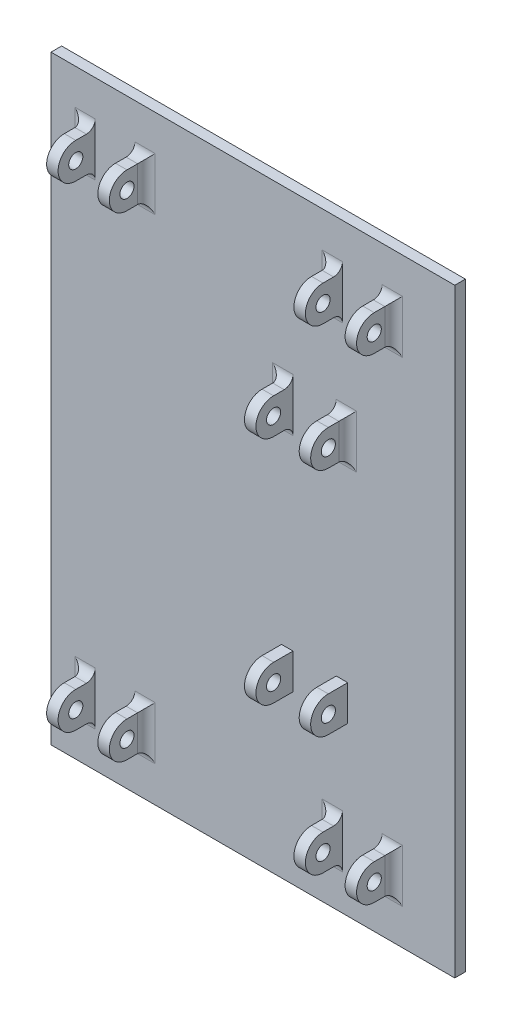
SolidWorks part; units mm, degrees
other "Markup3"
sketch "Sketch7" plane through (228.6, -342.9, 31.75) normal (0.076, -0.0024, 0.9971) x (0.9961, 0.0458, -0.0758)
other "Markup4"
sketch "Sketch8" plane through (228.6, -342.9, 31.75) normal (0.076, -0.0024, 0.9971) x (0.9961, 0.0458, -0.0758)
material "7075-T6 (SN)"
ref_plane "Front Plane" through (0, 0, 0) normal (0, 0, 1) x (1, 0, 0)
ref_plane "Top Plane" through (0, 0, 0) normal (0, 1, 0) x (1, 0, 0)
ref_plane "Right Plane" through (0, 0, 0) normal (1, 0, 0) x (0, 0, -1)
sketch "Sketch1" plane through (0, 0, 0) normal (0, 0, 1) x (1, 0, 0)
  line L1 (0, 0) -> (228.6, 0)
  line L2 (0, 0) -> (0, -339.725)
  line L3 (0, -339.725) -> (228.6, -339.725)
  line L4 (228.6, 0) -> (228.6, -339.725)
  dimension "D1" = 339.725
  dimension "D2" = 228.6
extrude "Boss-Extrude1" add sketch "Sketch1" along normal blind 6
sketch "Sketch2" plane through (0, 0, 6) normal (0, 0, 1) x (1, 0, 0)
  line L0 (0, 0) -> (0, -339.725) construction
  line L1 (25, -25.2425) -> (47.5, -25.2425) construction
  line L2 (25, -25.2425) -> (25, -45.2425)
  line L3 (25, -45.2425) -> (47.5, -45.2425) construction
  line L4 (47.5, -25.2425) -> (47.5, -45.2425)
  line L5 (165, -25.2425) -> (187.5, -25.2425) construction
  line L6 (165, -25.2425) -> (165, -45.2425)
  line L7 (165, -45.2425) -> (187.5, -45.2425) construction
  line L8 (187.5, -25.2425) -> (187.5, -45.2425)
  line L18 (137.0009, -114.5325) -> (137.0009, -225.1925) construction
  line L19 (0, -169.8625) -> (106.25, -169.8625) construction
  line L20 (54, -35.2425) -> (158.5, -35.2425) construction
  line L26 (165, -25.2425) -> (158.5, -25.2425)
  line L27 (165, -25.2425) -> (165, -45.2425)
  line L28 (165, -45.2425) -> (158.5, -45.2425)
  line L29 (158.5, -25.2425) -> (158.5, -45.2425)
  line L30 (187.5, -25.2425) -> (194, -25.2425)
  line L31 (187.5, -25.2425) -> (187.5, -45.2425)
  line L32 (187.5, -45.2425) -> (194, -45.2425)
  line L33 (194, -25.2425) -> (194, -45.2425)
  line L34 (47.5, -25.2425) -> (54, -25.2425)
  line L35 (47.5, -25.2425) -> (47.5, -45.2425)
  line L36 (47.5, -45.2425) -> (54, -45.2425)
  line L37 (54, -25.2425) -> (54, -45.2425)
  line L38 (25, -25.2425) -> (18.5, -25.2425)
  line L39 (25, -25.2425) -> (25, -45.2425)
  line L40 (25, -45.2425) -> (18.5, -45.2425)
  line L41 (18.5, -25.2425) -> (18.5, -45.2425)
  line L65 (228.6, -339.725) -> (228.6, 0) construction
  line L66 (137.0009, -225.1925) -> (161.5009, -225.1925) construction
  line L67 (158.5, -304.4825) -> (194, -304.4825) construction
  line L68 (149.2509, -104.5325) -> (149.2509, -229.5652) construction
  line L76 (18.5, -35.2425) -> (54, -35.2425) construction
  line L77 (18.5, -304.4825) -> (54, -304.4825) construction
  line L78 (36.25, -35.2425) -> (36.25, -304.4825) construction
  line L79 (137.0009, -94.5325) -> (161.5009, -94.5325) construction
  line L80 (54, -304.4825) -> (158.5, -304.4825) construction
  line L81 (106.25, -35.2425) -> (106.25, -304.4825) construction
  line L82 (106.25, -169.8625) -> (228.6, -169.8625) construction
  line L83 (130.5009, -94.5325) -> (130.5009, -114.5325)
  line L84 (137.0009, -114.5325) -> (130.5009, -114.5325)
  line L86 (137.0009, -94.5325) -> (130.5009, -94.5325)
  line L88 (137.0009, -94.5325) -> (137.0009, -114.5325)
  line L89 (161.5009, -114.5325) -> (168.0009, -114.5325)
  line L90 (161.5009, -114.5325) -> (161.5009, -94.5325)
  line L91 (168.0009, -94.5325) -> (168.0009, -114.5325)
  line L92 (161.5009, -94.5325) -> (168.0009, -94.5325)
  line L93 (130.5009, -235.1925) -> (168.0009, -235.1925) construction
  line L96 (137.0009, -245.1925) -> (161.5009, -245.1925) construction
  line L97 (161.5009, -245.1925) -> (168.0009, -245.1925)
  line L98 (168.0009, -245.1925) -> (168.0009, -225.1925)
  line L103 (130.5009, -104.5325) -> (168.0009, -104.5325) construction
  line L104 (137.0009, -114.5325) -> (161.5009, -114.5325) construction
  line L106 (158.5, -35.2425) -> (194, -35.2425) construction
  line L108 (176.25, -35.2425) -> (176.25, -304.4825) construction
  line L109 (165, -294.4825) -> (187.5, -294.4825) construction
  line L112 (165, -314.4825) -> (187.5, -314.4825) construction
  line L113 (25, -294.4825) -> (47.5, -294.4825) construction
  line L114 (25, -314.4825) -> (47.5, -314.4825) construction
  line L117 (161.5009, -114.5325) -> (161.5009, -225.1925) construction
  line L118 (18.5, -314.4825) -> (18.5, -294.4825)
  line L119 (25, -294.4825) -> (18.5, -294.4825)
  line L120 (25, -314.4825) -> (25, -294.4825)
  line L121 (25, -314.4825) -> (18.5, -314.4825)
  line L122 (54, -314.4825) -> (54, -294.4825)
  line L123 (47.5, -294.4825) -> (54, -294.4825)
  line L124 (47.5, -314.4825) -> (47.5, -294.4825)
  line L125 (47.5, -314.4825) -> (54, -314.4825)
  line L126 (194, -314.4825) -> (194, -294.4825)
  line L127 (187.5, -294.4825) -> (194, -294.4825)
  line L128 (187.5, -314.4825) -> (187.5, -294.4825)
  line L129 (187.5, -314.4825) -> (194, -314.4825)
  line L130 (158.5, -314.4825) -> (158.5, -294.4825)
  line L131 (165, -294.4825) -> (158.5, -294.4825)
  line L132 (165, -314.4825) -> (165, -294.4825)
  line L133 (165, -314.4825) -> (158.5, -314.4825)
  line L134 (187.5, -314.4825) -> (187.5, -294.4825)
  line L135 (165, -314.4825) -> (165, -294.4825)
  line L136 (47.5, -314.4825) -> (47.5, -294.4825)
  line L137 (25, -314.4825) -> (25, -294.4825)
  line L138 (161.5009, -225.1925) -> (161.5009, -245.1925)
  line L139 (161.5009, -225.1925) -> (168.0009, -225.1925)
  line L140 (137.0009, -245.1925) -> (137.0009, -225.1925)
  line L141 (137.0009, -245.1925) -> (130.5009, -245.1925)
  line L142 (137.0009, -225.1925) -> (130.5009, -225.1925)
  line L143 (130.5009, -245.1925) -> (130.5009, -225.1925)
  point P63 (194, -35.2425)
  point P70 (0, 0)
  point P101 (228.6, -169.8625)
  point P103 (158.5, -35.2425)
  dimension "D5" = 43.0009
  dimension "D1" = 20
  dimension "D2" = 22.5
  dimension "D3" = 6.5
  dimension "D4" = 199.95
  dimension "D6" = 134.62
  dimension "D7" = 134.62
  dimension "D8" = 24.5
  dimension "D9" = 70
  dimension "D10" = 25
extrude "Boss-Extrude2" add sketch "Sketch2" along normal blind 24 contours L133 L132 L131 L130 | L128 L129 L126 L127 | L139 L138 L97 L98 | L143 L141 L140 L142 | L124 L125 L122 L123 | L121 L120 L119 L118 | L92 L90 L89 L91 | L88 L86 L83 L84 | L33 L30 L8 L32 | L37 L34 L4 L36 | L38 L41 L40 L2 | L26 L29 L28 L27 region at (21.75, -35.2425, 6) region at (50.75, -35.2425, 6) region at (190.75, -35.2425, 6) region at (133.7509, -104.5325, 6) region at (164.7509, -104.5325, 6) region at (164.7509, -235.1925, 6) region at (21.75, -304.4825, 6) region at (50.75, -304.4825, 6) region at (190.75, -304.4825, 6) region at (161.75, -304.4825, 6) region at (133.7509, -235.1925, 6)
sketch "Sketch3" plane through (18.5, 0, 0) normal (-1, 0, 0) x (0, 0, 1)
  line L0 (17, -104.5325) -> (6, -104.5325) construction
  line L1 (17, -304.4825) -> (6, -304.4825) construction
  line L2 (21, -235.1925) -> (37.7332, -235.1925) construction
  line L3 (21, -235.1925) -> (6, -235.1925) construction
  line L4 (17, -35.2425) -> (6, -35.2425) construction
  line L5 (6, -25.2425) -> (6, -45.2425) construction
  line L6 (6, -245.1925) -> (6, -225.1925) construction
  line L7 (6, 0) -> (6, -339.725) construction
  line L9 (17, -25.2425) -> (17, -12.9829)
  line L10 (17, -12.9829) -> (50.9495, -12.9829)
  line L11 (6, -245.1925) -> (6, -225.1925) construction
  line L12 (50.9495, -12.9829) -> (50.9495, -57.481)
  line L13 (50.9495, -57.481) -> (17, -57.481)
  line L14 (17, -57.481) -> (17, -45.2425)
  line L15 (51.4423, -132.3991) -> (17, -132.3991)
  line L16 (17, -94.5325) -> (17, -71.5915)
  line L17 (17, -71.5915) -> (51.4423, -71.5915)
  line L18 (17, -132.3991) -> (17, -114.5325)
  line L19 (51.4423, -71.5915) -> (51.4423, -132.3991)
  line L20 (51.5995, -270.3754) -> (17, -270.3754)
  line L21 (17, -225.1925) -> (17, -207.3064)
  line L22 (17, -207.3064) -> (51.5995, -207.3064)
  line L23 (17, -270.3754) -> (17, -245.1925)
  line L24 (51.5995, -207.3064) -> (51.5995, -270.3754)
  line L25 (51.621, -326.7211) -> (17, -326.7211)
  line L26 (17, -294.4825) -> (17, -282.2228)
  line L27 (17, -282.2228) -> (51.621, -282.2228)
  line L28 (17, -326.7211) -> (17, -314.4825)
  line L29 (51.621, -282.2228) -> (51.621, -326.7211)
  line L30 (6, -94.5325) -> (6, -114.5325) construction
  line L31 (30, -25.2425) -> (6, -25.2425) construction
  line L32 (30, -94.5325) -> (6, -94.5325) construction
  line L35 (6, -314.4825) -> (6, -294.4825) construction
  line L36 (6, -314.4825) -> (6, -294.4825) construction
  line L37 (17, -35.2425) -> (17, -104.5325) construction
  line L38 (17, -104.5325) -> (17, -235.1925) construction
  line L39 (17, -235.1925) -> (17, -304.4825) construction
  line L41 (30, -225.1925) -> (6, -225.1925) construction
  circle A0 centre (17, -35.2425) radius 4
  circle A1 centre (17, -235.1925) radius 4
  circle A2 centre (17, -35.2425) radius 5.5 construction
  circle A3 centre (17, -304.4825) radius 4
  circle A4 centre (17, -104.5325) radius 4
  arc A5 (17, -45.2425) -> (17, -25.2425) centre (17, -35.2425) ccw
  arc A6 (17, -114.5325) -> (17, -94.5325) centre (17, -104.5325) ccw
  arc A7 (17, -245.1925) -> (17, -225.1925) centre (17, -235.1925) ccw
  arc A8 (17, -314.4825) -> (17, -294.4825) centre (17, -304.4825) ccw
  point P5 (0, 0)
  point P26 (0, 0)
  point P52 (0, 0)
  point P61 (0, 0)
  point P62 (6, -304.4825)
  point P63 (17, -229.9825)
  point P67 (6, -235.1925)
  dimension "D1" = 8
  dimension "D2" = 8
  dimension "D4" = 11
  dimension "D3" = 11
extrude "Cut-Extrude1" cut sketch "Sketch3" against normal through all both and the other way through all
fillet "Fillet2" radius 5 30 edges at (158.5, -304.4825, 6) (18.5, -304.4825, 6) (21.75, -45.2425, 6) (18.5, -35.2425, 6) (21.75, -25.2425, 6) (50.75, -25.2425, 6) (50.75, -45.2425, 6) (54, -35.2425, 6) (161.75, -25.2425, 6) (190.75, -25.2425, 6) (194, -35.2425, 6) (190.75, -45.2425, 6) (161.75, -45.2425, 6) (158.5, -35.2425, 6) (168.0009, -104.5325, 6) (164.7509, -114.5325, 6) (133.7509, -114.5325, 6) (130.5009, -104.5325, 6) (164.7509, -94.5325, 6) (133.7509, -94.5325, 6) (21.75, -294.4825, 6) (50.75, -294.4825, 6) (54, -304.4825, 6) (194, -304.4825, 6) (161.75, -294.4825, 6) (190.75, -294.4825, 6) (190.75, -314.4825, 6) (161.75, -314.4825, 6) (50.75, -314.4825, 6) (21.75, -314.4825, 6)
sketch "Sketch5" [suppressed] plane through (0, 0, 6.35) normal (0, 0, 1) x (1, 0, 0)
  line L0 (228.6, 0) -> (0, 0) construction
  line L1 (0, 0) -> (0, -339.725) construction
  line L2 (228.6, -339.725) -> (228.6, 0) construction
  line L3 (141.304, -49.7675) -> (141.304, -20.7175) construction
  line L4 (141.304, -49.7675) -> (141.304, -20.7175)
  line L5 (141.304, -49.7675) -> (183.308, -49.7675) construction
  line L6 (141.304, -35.2425) -> (56.054, -35.2425) construction
  line L7 (56.054, -20.7175) -> (56.054, -49.7675) construction
  line L8 (162.306, -49.7675) -> (162.306, -77.4398) construction
  line L9 (13.796, -49.7675) -> (56.054, -49.7675) construction
  line L10 (25.4, -49.7675) -> (14.05, -49.7675) construction
  line L11 (34.925, -49.7675) -> (34.925, -74.5657) construction
  line L12 (186.728, -115.063) -> (195.112, -115.063) construction
  line L13 (195.112, -115.063) -> (190.92, -115.063) construction
  line L14 (190.92, -115.063) -> (190.92, -77.4398) construction
  line L15 (190.92, -77.4398) -> (190.92, -189.3922) construction
  line L16 (164.378, -150.113) -> (164.378, -115.063) construction
  line L17 (217.462, -150.113) -> (195.112, -150.113) construction
  line L18 (160.654, -286.9575) -> (163.958, -286.9575) construction
  line L19 (33.4, -286.9575) -> (36.704, -286.9575) construction
  line L20 (36.704, -286.9575) -> (35.052, -286.9575) construction
  line L21 (35.052, -286.9575) -> (35.052, -271.8353) construction
  line L22 (162.306, -286.9575) -> (162.306, -271.8353) construction
  line L23 (59.054, -304.4825) -> (138.304, -304.4825) construction
  line L24 (59.054, -286.9575) -> (59.054, -322.0075) construction
  line L25 (138.304, -322.0075) -> (138.304, -286.9575) construction
  line L26 (0, -339.725) -> (228.6, -339.725) construction
  circle A0 centre (12.7, -12.7) radius 3.175
  circle A1 centre (215.9, -12.7) radius 3.175
  circle A2 centre (62.404, -35.2425) radius 3.175
  circle A3 centre (134.954, -35.2425) radius 3.175
  circle A4 centre (162.306, -56.1175) radius 3.175
  circle A5 centre (34.925, -56.1175) radius 3.175
  circle A6 centre (190.92, -108.713) radius 3.175
  circle A7 centre (158.028, -136.1329) radius 3.175
  circle A8 centre (190.92, -156.463) radius 3.175
  circle A9 centre (35.052, -280.6075) radius 3.175
  circle A10 centre (65.404, -304.4825) radius 3.175
  circle A11 centre (12.7, -327.025) radius 3.175
  circle A12 centre (215.9, -327.025) radius 3.175
  circle A13 centre (131.954, -304.4825) radius 3.175
  circle A14 centre (162.306, -280.6075) radius 3.175
  dimension "D1" = 12.7
  dimension "D3" = 12.7
  dimension "D5" = 6.35
  dimension "D6" = 6.35
  dimension "D7" = 6.35
  dimension "D8" = 6.35
  dimension "D9" = 6.35
  dimension "D10" = 6.35
  dimension "D11" = 6.35
  dimension "D12" = 6.35
  dimension "D13" = 6.35
  dimension "D14" = 6.35
  dimension "D15" = 6.35
  dimension "D17" = 12.7
  dimension "D18" = 12.7
  dimension "D19" = 12.7
  dimension "D2" = 12.7
  dimension "D4" = 12.7
  dimension "D16" = 12.7
extrude "Cut-Extrude2" [suppressed] cut sketch "Sketch5" against normal through all contours A0 | A5 | A3 | A1 | A4 | A6 | A7 | A8 | A12 | A14 | A13 | A10 | A9 | A11
sketch "Sketch9" [suppressed] plane through (0, 0, 6.35) normal (0, 0, 1) x (1, 0, 0)
  line L5 (228.6, -339.725) -> (228.6, 0) construction
  line L6 (164.378, -181.863) -> (209.55, -181.863)
  line L7 (164.378, -181.863) -> (164.378, -255.525)
  line L8 (164.378, -255.525) -> (209.55, -255.525)
  line L9 (209.55, -181.863) -> (209.55, -255.525)
  line L10 (164.378, -181.863) -> (209.55, -255.525)
  line L11 (171.8269, -181.863) -> (209.55, -243.3781)
  line L12 (164.378, -194.0099) -> (202.1011, -255.525)
  line L14 (158.9648, -185.1826) -> (204.1368, -258.8446) construction
  line L15 (169.7912, -178.5434) -> (214.9632, -252.2054) construction
  circle A3 centre (162.306, -280.925) radius 3.175 construction
  circle A4 centre (190.92, -156.463) radius 3.175 construction
  dimension "D4" = 25.4
  dimension "D7" = 25.4
  dimension "D6" = 19.05
  dimension "D8" = 6.35
  dimension "D9" = 6.35
extrude "Cut-Extrude3" [suppressed] cut sketch "Sketch9" against normal through all contours L12 L7 L8 | L6 L11 L9
fillet "Fillet4" [suppressed] radius 6.35
move or copy body "Body-Move/Copy2" [suppressed] bodies to move or copy 105
move or copy body "Body-Move/Copy1" [suppressed] bodies to move or copy 105
